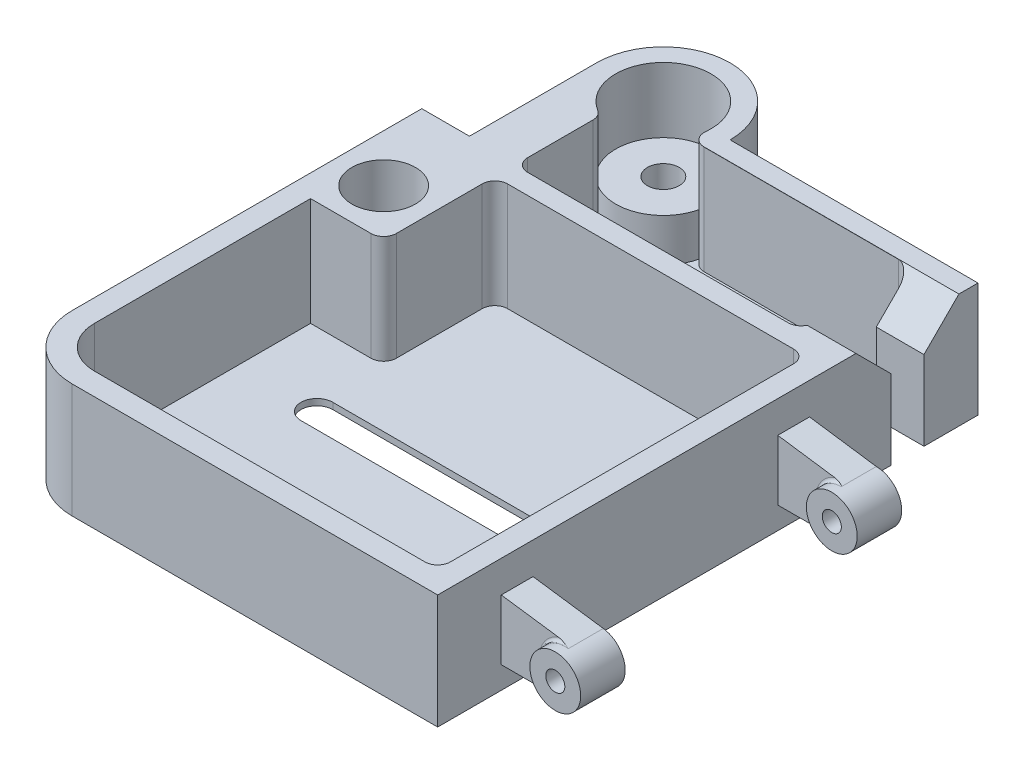
SolidWorks part; units mm, degrees
ref_plane "Front Plane" through (0, 0, 0) normal (0, 0, 1) x (1, 0, 0)
ref_plane "Top Plane" through (0, 0, 0) normal (0, 1, 0) x (1, 0, 0)
ref_plane "Right Plane" through (0, 0, 0) normal (1, 0, 0) x (0, 0, -1)
sketch "Sketch1" plane through (0, 0, 0) normal (0, 1, 0) x (1, 0, 0)
  line L0 (56.5, 58) -> (-33.5, 58)
  line L1 (67.5, -65) -> (-47.5, -65)
  line L2 (67.5, -65) -> (67.5, 65)
  line L4 (-67.5, -45) -> (-67.5, 65)
  line L5 (67.5, -65) -> (-67.5, 65) construction
  line L6 (67.5, 65) -> (-67.5, -65) construction
  line L7 (-60.5, -45) -> (-60.5, 23)
  line L8 (56.5, -58) -> (-47.5, -58)
  line L9 (60.5, -54) -> (60.5, 54)
  line L10 (-67.5, 65) -> (-52.5, 65) construction
  line L13 (-67.5, 65) -> (-52.5, 65) construction
  line L14 (-60.5, -45) -> (-60.5, 58) construction
  line L15 (-52.5, 65) -> (-52.5, 105)
  line L16 (60.5, 58) -> (-60.5, 58) construction
  line L18 (-52.5, 65) -> (-67.5, 65)
  line L19 (67.5, 0) -> (35.5, 0) construction
  line L20 (67.5, 65) -> (-67.5, 65) construction
  line L21 (-67.5, 0) -> (-35.5, 0) construction
  line L22 (-35.5, 0) -> (35.5, 0) construction
  line L23 (-35.5, 5) -> (35.5, 5)
  line L24 (-35.5, -5) -> (35.5, -5)
  line L26 (-67.5, -65) -> (-67.5, 38) construction
  line L27 (-37.5, 54) -> (-37.5, 27)
  line L28 (-41.5, 23) -> (-60.5, 23)
  line L29 (-60.5, 23) -> (-67.5, 23)
  line L30 (67.5, 65) -> (67.5, 105)
  line L31 (77.4983, -65) -> (77.4983, -35) construction
  line L32 (77.4983, -35) -> (77.4983, 52) construction
  line L33 (-33.5, 64.3) -> (48.5, 64.3)
  line L34 (-12.6088, 98.97) -> (48.5, 98.97)
  line L35 (52.5, 94.97) -> (52.5, 68.3)
  line L36 (67.5, 105) -> (-10.5, 105)
  line L37 (-37.5, 58) -> (-37.5, 64.3) construction
  line L38 (-37.5, 68.3) -> (-37.5, 88.8445)
  line L39 (60.5, -58) -> (60.5, 58) construction
  line L40 (60.5, -58) -> (-47.5, -58) construction
  arc A0 (-47.5, -65) -> (-67.5, -45) centre (-47.5, -45) cw
  arc A1 (-47.5, -58) -> (-60.5, -45) centre (-47.5, -45) cw
  arc A2 (-35.5, 5) -> (-35.5, -5) centre (-35.5, 0) ccw
  arc A3 (35.5, -5) -> (35.5, 5) centre (35.5, 0) ccw
  circle A4 centre (-52.5, 38) radius 10
  arc A8 (-10.5, 105) -> (-52.5, 105) centre (-31.5, 105) ccw
  arc A9 (-16.5859, 103.3974) -> (-39.3947, 92.2457) centre (-31.5, 105) ccw
  arc A10 (-12.6088, 98.97) -> (-16.5859, 103.3974) centre (-12.6088, 102.97) cw
  arc A11 (-37.5, 88.8445) -> (-39.3947, 92.2457) centre (-41.5, 88.8445) ccw
  arc A12 (60.5, -54) -> (56.5, -58) centre (56.5, -54) cw
  arc A13 (-33.5, 64.3) -> (-37.5, 68.3) centre (-33.5, 68.3) cw
  arc A14 (52.5, 94.97) -> (48.5, 98.97) centre (48.5, 94.97) ccw
  arc A15 (48.5, 64.3) -> (52.5, 68.3) centre (48.5, 68.3) ccw
  arc A16 (60.5, 54) -> (56.5, 58) centre (56.5, 54) ccw
  arc A17 (-37.5, 54) -> (-33.5, 58) centre (-33.5, 54) cw
  arc A18 (-41.5, 23) -> (-37.5, 27) centre (-41.5, 27) ccw
  point P0 (0, 0)
  point P26 (0, 0)
  point P66 (-37.5, 23)
  dimension "D2" = 20
  dimension "D9" = 5
  dimension "D11" = 20
  dimension "D13" = 15
  dimension "D19" = 6.03
  dimension "D16" = 40
  dimension "D20" = 21
  dimension "D21" = 30
  dimension "D22" = 4
  dimension "D23" = 4
  dimension "D24" = 4
  dimension "D1" = 130
  dimension "D3" = 115
  dimension "D5" = 35
  dimension "D6" = 30
  dimension "D7" = 32
  dimension "D8" = 32
  dimension "D10" = 103
  dimension "D4" = 7
  dimension "D12" = 15
  dimension "D14" = 30
  dimension "D15" = 87
  dimension "D17" = 99
  dimension "D18" = 6.3
extrude "Boss-Extrude1" add sketch "Sketch1" along normal blind 36 contours L36 A8 L15 L18 L4 L28 L27 L0 L9 L8 A1 L7 A0 L1 L2 L30 A4 L38 A11 A9 A10 L34 L35 L33 region at (-65.1611, 0, -44)
extrude "Boss-Extrude2" add sketch "Sketch1<5>" along normal blind 2 contours A1 L8 L9 L0 L27 L28 L7 A3 L24 A2 L23 | A11 L38 L33 L35 L34 A10 A9 region at (58.1432, 0, -55.6432) region at (1.3215, 0, -85.6533)
sketch "Sketch1<5>" plane through (0, 0, 0) normal (0, 1, 0) x (1, 0, 0) same geometry as "Sketch1"
sketch "Sketch2" plane through (0, 2, 0) normal (0, 1, 0) x (1, 0, 0)
  circle A0 centre (-31.5, 105) radius 15
extrude "Boss-Extrude3" add sketch "Sketch2" along normal blind 13.5
ref_plane "Plane1" through (0, 0, 35) normal (0, 0, 1) x (1, 0, 0)
sketch "Sketch3" plane through (0, 0, 35) normal (0, 0, 1) x (1, 0, 0)
  line L0 (67.5, 0) -> (-47.5, 0) construction
  line L1 (67.5, 36) -> (67.5, 0) construction
  line L2 (67.5, 36) -> (67.5, 26) construction
  line L3 (67.5, 26) -> (89.6028, 22.9236)
  line L4 (88.5, 7) -> (67.5, 7)
  line L5 (67.5, 26) -> (67.5, 7)
  circle A0 centre (88.5, 15) radius 8
  circle A1 centre (88.5, 15) radius 3
  dimension "D1" = 16
  dimension "D2" = 6
  dimension "D3" = 15
  dimension "D4" = 21
  dimension "D5" = 10
extrude "Boss-Extrude4" add sketch "Sketch3" along normal blind 10 contours A0 L3 L5 L4 region at (74.933, 16.0867, 35)
extrude "Boss-Extrude5" add sketch "Sketch3<4>" along normal blind 14 contours A0 A1 region at (94.3635, 20.1039, 35)
sketch "Sketch3<4>" plane through (0, 0, 35) normal (0, 0, 1) x (1, 0, 0) same geometry as "Sketch3"
sketch "Sketch5" plane through (0, 36, 0) normal (0, 1, 0) x (1, 0, 0)
  line L0 (67.5, -35) -> (67.5, 52) construction
  line L1 (67.5, -65) -> (67.5, 105) construction
  line L2 (44.0151, 8.5) -> (97.9489, 8.5) construction
  dimension "D1" = 87
ref_plane "Plane3" through (0, 0, -52) normal (0, 0, 1) x (1, 0, 0)
sketch "Sketch6" plane through (0, 0, -52) normal (0, 0, 1) x (1, 0, 0)
  line L0 (67.5, 26) -> (88.5, 23)
  line L1 (67.5, 26) -> (67.5, 7)
  line L2 (67.5, 7) -> (88.5, 7)
  circle A0 centre (88.5, 15) radius 3
  circle A1 centre (88.5, 15) radius 8
  dimension "D1" = 6
extrude "Boss-Extrude6" add sketch "Sketch6" along normal blind 10 contours A1 L0 L1 L2 region at (74.9117, 16.0619, -52)
extrude "Boss-Extrude7" add sketch "Sketch6<3>" along normal blind 14 contours A1 A0 region at (93.9969, 20.4969, -52)
sketch "Sketch6<3>" plane through (0, 0, -52) normal (0, 0, 1) x (1, 0, 0) same geometry as "Sketch6"
sketch "Sketch7" plane through (0, 15.5, 0) normal (0, 1, 0) x (1, 0, 0)
  circle A0 centre (-31.5, 105) radius 5
  dimension "D1" = 10
extrude "Cut-Extrude1" cut sketch "Sketch7" against normal through all
sketch "Sketch8" plane through (0, 36, 0) normal (0, 1, 0) x (1, 0, 0)
  line L0 (67.5, 105) -> (67.5, 72) construction
  line L1 (67.5, -65) -> (67.5, 105) construction
  line L2 (62.6428, 105) -> (62.6428, 77.6) construction
  line L3 (67.5, 105) -> (-10.5, 105) construction
  line L4 (52.5, 72) -> (67.5, 72)
  line L5 (52.5, 94.97) -> (52.5, 68.3) construction
  line L6 (52.5, 77.6) -> (67.5, 77.6)
  line L7 (52.5, 94.97) -> (52.5, 68.3) construction
  line L8 (52.5, 77.6) -> (52.5, 72)
  line L9 (67.5, 77.6) -> (67.5, 72)
  line L10 (52.5, 94) -> (67.5, 94)
  line L11 (52.5, 88) -> (67.5, 88)
  line L12 (52.5, 94) -> (52.5, 88)
  line L13 (67.5, 94) -> (67.5, 88)
  line L14 (52.5, 88) -> (52.5, 77.6)
  line L15 (67.5, 77.6) -> (52.5, 77.6)
  line L16 (67.5, 77.6) -> (67.5, 88)
  line L17 (52.5, 88) -> (67.5, 88)
  line M9 (67.5, -65) -> (67.5, 105)
  line M27 (52.5, 94.97) -> (52.5, 68.3)
  dimension "D1" = 33
  dimension "D2" = 27.4
  dimension "D3" = 11
  dimension "D4" = 17
extrude "Cut-Extrude2" cut sketch "Sketch8" against normal through all contours L11 L6 M27 M9 region at (60, 36, -82.8)
chamfer "Chamfer1" distance 11 angle 45 2 edges at (60, 36, -88) (60, 36, -77.6)
fillet "Fillet1" radius 1 2 edges at (80.5, 15, -42) (80.5191, 15.5527, 45)
